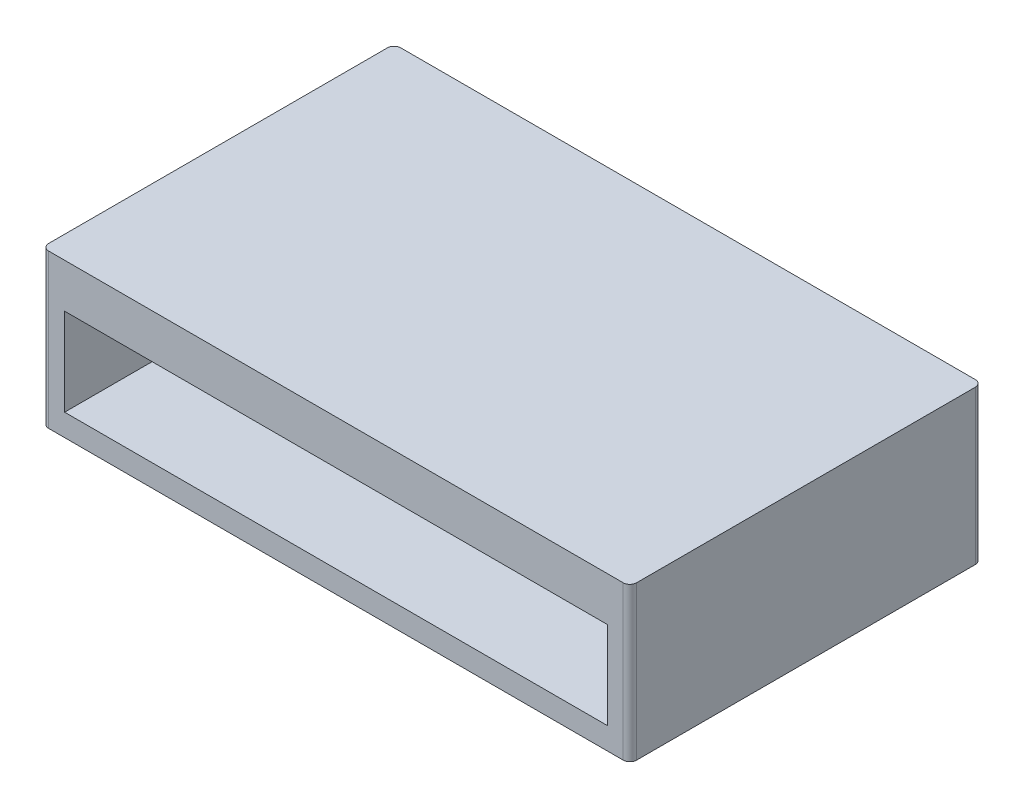
SolidWorks part; units mm, degrees
ref_plane "Front Plane" through (0, 0, 0) normal (0, 0, 1) x (1, 0, 0)
ref_plane "Top Plane" through (0, 0, 0) normal (0, 1, 0) x (1, 0, 0)
ref_plane "Right Plane" through (0, 0, 0) normal (1, 0, 0) x (0, 0, -1)
sketch "Sketch1" plane through (0, 0, 0) normal (0, 1, 0) x (1, 0, 0)
  line L1 (0, 0) -> (88, 0)
  line L2 (0, 0) -> (0, 52.7)
  line L3 (0, 52.7) -> (88, 52.7)
  line L4 (88, 0) -> (88, 52.7)
  dimension "D1" = 88
  dimension "D2" = 52.7
extrude "Boss-Extrude1" add sketch "Sketch1" along normal blind 23
sketch "Sketch2" plane through (0, 0, 0) normal (0, 0, 1) x (1, 0, 0)
  line L1 (3.375, 16.4) -> (84.625, 16.4)
  line L2 (3.375, 16.4) -> (3.375, 3.3)
  line L3 (3.375, 3.3) -> (84.625, 3.3)
  line L4 (84.625, 16.4) -> (84.625, 3.3)
extrude "Cut-Extrude1" cut sketch "Sketch2" against normal blind 15.75
sketch "Sketch3" plane through (0, 0, 0) normal (-1, 0, 0) x (0, 0, 1)
  line L0 (-41.37, 16) -> (-33.03, 16) construction
  line L1 (-40.09, 14.72) -> (-34.31, 14.72)
  line L2 (-40.09, 14.72) -> (-40.09, 17.28)
  line L3 (-40.09, 17.28) -> (-34.31, 17.28)
  line L4 (-34.31, 14.72) -> (-34.31, 17.28)
  line L5 (-37.2, 17.28) -> (-37.2, 14.72) construction
  line L6 (-52.7, 23) -> (-52.7, 0) construction
  line L7 (-52.7, 23) -> (0, 23) construction
  circle A0 centre (-40.09, 16) radius 1.28
  circle A1 centre (-34.31, 16) radius 1.28
  dimension "D1" = 8.34
  dimension "D2" = 2.56
  dimension "D3" = 15.5
  dimension "D4" = 7
extrude "Cut-Extrude2" cut sketch "Sketch3" against normal blind 6.5 contours L2 A0 | L2 A0 | A1 L3 A0 L1 | L4 A1 | L4 A1 region at (0, 16, -37.2) region at (0, 16, -40.6332) region at (0, 16, -39.5468) region at (0, 16, -34.8532) region at (0, 16, -33.7668)
sketch "Sketch4" plane through (6.5, 0, 0) normal (-1, 0, 0) x (0, 0, 1)
  line L0 (-37.2, 17.28) -> (-37.2, 14.72) construction
  line L3 (-40.09, 17.28) -> (-34.31, 17.28) construction
  line L4 (-40.545, 15.6) -> (-33.855, 15.6)
  line L5 (-40.545, 15.6) -> (-40.545, 16.4)
  line L6 (-40.545, 16.4) -> (-33.855, 16.4)
  line L7 (-33.855, 15.6) -> (-33.855, 16.4)
  line L8 (-40.545, 15.6) -> (-33.855, 16.4) construction
  line L9 (-40.545, 16.4) -> (-33.855, 15.6) construction
  line L10 (-40.09, 14.72) -> (-34.31, 14.72) construction
  point P6 (-37.2, 16)
  dimension "D1" = 6.69
  dimension "D2" = 0.8
extrude "Boss-Extrude2" add sketch "Sketch4" along normal offset from surface (6 mm away) 0.5 up to face at (0, 16, -37.2)
fillet "Fillet1" radius 1 4 edges at (88, 11.5, 0) (88, 11.5, -52.7) (0, 11.5, -52.7) (0, 11.5, 0)
sketch "Sketch5" plane through (0, 0, 0) normal (0, -1, 0) x (1, 0, 0)
  line L0 (44, 0) -> (44, -8.6) construction
  line L3 (1, 0) -> (87, 0) construction
  line L4 (3.75, -44.1) -> (84.25, -44.1) construction
  line L5 (3.75, -44.1) -> (3.75, -8.6) construction
  line L6 (3.75, -8.6) -> (84.25, -8.6) construction
  line L7 (84.25, -44.1) -> (84.25, -8.6) construction
  line L8 (3.75, -44.1) -> (84.25, -8.6) construction
  line L9 (3.75, -8.6) -> (84.25, -44.1) construction
  line L10 (44, -44.1) -> (44, -52.7) construction
  line L11 (87, -52.7) -> (1, -52.7) construction
  point P12 (3.75, -8.6)
  point P13 (3.75, -44.1)
  point P14 (84.25, -44.1)
  point P15 (84.25, -8.6)
  dimension "D1" = 80.5
  dimension "D2" = 35.5
sketch "Sketch6" plane through (0, 0, 0) normal (0, -1, 0) x (1, 0, 0)
  line L1 (3, -13.1) -> (4.5, -13.1)
  line L2 (3, -13.1) -> (3, -4.1)
  line L3 (3, -4.1) -> (4.5, -4.1)
  line L4 (4.5, -13.1) -> (4.5, -4.1)
  line L5 (3, -13.1) -> (4.5, -4.1) construction
  line L6 (3, -4.1) -> (4.5, -13.1) construction
  point P0 (3.75, -8.6)
  dimension "D1" = 9
  dimension "D2" = 1.5
extrude "Boss-Extrude3" add sketch "Sketch6" along normal blind 1
chamfer "Chamfer1" distance 1 angle 45 2 edges at (3.75, -1, -4.1) (3.75, -1, -13.1)
pattern_sketch "Sketch-Pattern1" of "Chamfer1", "Boss-Extrude3" driven by "Sketch5"
sketch "Sketch7" plane through (0, 0, 0) normal (0, -1, 0) x (1, 0, 0)
  line L0 (44, 0) -> (44, -52.7) construction
  line L1 (1, 0) -> (87, 0) construction
  line L2 (87, -52.7) -> (1, -52.7) construction
  line L3 (9.75, -26.35) -> (78.25, -26.35) construction
  point P9 (44, -26.35)
  point P10 (9.75, -26.35)
  point P11 (78.25, -26.35)
  dimension "D1" = 68.5
sketch "Sketch8" plane through (0, 0, 0) normal (0, -1, 0) x (1, 0, 0)
  point P0 (9.75, -26.35)
  point P1 (78.25, -26.35)
sketch "Sketch9" plane through (0, 0, 0) normal (0, -1, 0) x (1, 0, 0)
  line L0 (9.75, -31.85) -> (9.75, -20.85) construction
  line L1 (7.75, -31.85) -> (7.75, -20.85)
  line L2 (11.75, -31.85) -> (11.75, -20.85)
  line L3 (9.75, -31.85) -> (9.75, -20.85) construction
  line L4 (4.75, -31.85) -> (4.75, -20.85)
  line L5 (14.75, -31.85) -> (14.75, -20.85)
  circle A0 centre (9.75, -26.35) radius 5
  arc A1 (7.75, -31.85) -> (11.75, -31.85) centre (9.75, -31.85) ccw
  arc A2 (11.75, -20.85) -> (7.75, -20.85) centre (9.75, -20.85) ccw
  arc A3 (4.75, -31.85) -> (14.75, -31.85) centre (9.75, -31.85) ccw
  arc A4 (14.75, -20.85) -> (4.75, -20.85) centre (9.75, -20.85) ccw
  point P5 (9.75, -26.35)
  point P12 (9.75, -26.35)
  dimension "D1" = 10
  dimension "D4" = 10
  dimension "D2" = 4
  dimension "D3" = 11
extrude "Cut-Extrude3" cut sketch "Sketch9" against normal blind 4 contours L2 A0 | L2 A0 L1 | L1 A0 | L2 A2 L1 A0 | L1 A1 L2 A0 region at (9.75, 0, -32.3587) region at (6.5125, 0, -26.35) region at (9.75, 0, -26.35) region at (9.75, 0, -20.3413) region at (12.9875, 0, -26.35)
extrude "Cut-Extrude4" cut sketch "Sketch9<3>" against normal up to surface (4 mm away) from offset 1.5 contours L4 A3 L5 A0 L2 A1 L1 | L5 A4 L4 A0 L1 A2 L2 region at (9.75, 0, -33.995) region at (5.4454, 0, -23.532) up to face at (9.75, 4, -26.35) offset against normal yes
sketch "Sketch9<3>" plane through (0, 0, 0) normal (0, -1, 0) x (1, 0, 0) same geometry as "Sketch9"
pattern_sketch "Sketch-Pattern2" of "Cut-Extrude3", "Cut-Extrude4" driven by "Sketch8"
